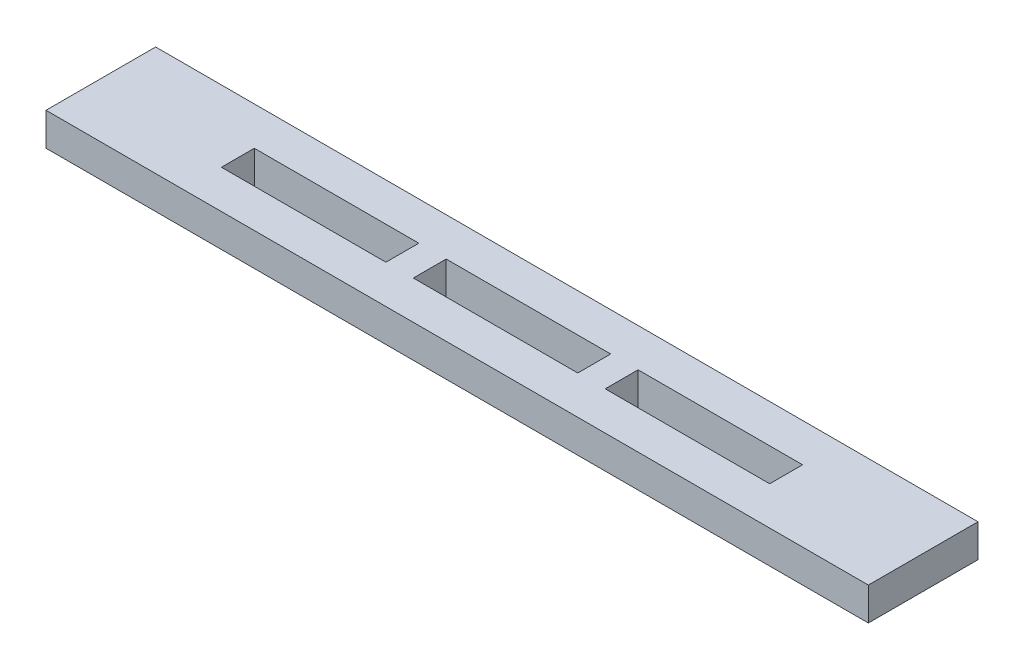
SolidWorks part; units mm, degrees
ref_plane "Front Plane" through (0, 0, 0) normal (0, 0, 1) x (1, 0, 0)
ref_plane "Top Plane" through (0, 0, 0) normal (0, 1, 0) x (1, 0, 0)
ref_plane "Right Plane" through (0, 0, 0) normal (1, 0, 0) x (0, 0, -1)
sketch "Sketch1" plane through (0, 0, 0) normal (0, 1, 0) x (1, 0, 0)
  line L1 (-75, 10) -> (75, 10)
  line L2 (-75, 10) -> (-75, -10)
  line L3 (-75, -10) -> (75, -10)
  line L4 (75, 10) -> (75, -10)
  line L5 (-75, 10) -> (75, -10) construction
  line L6 (-75, -10) -> (75, 10) construction
  point P0 (0, 0)
  dimension "D2" = 20
  dimension "D1" = 150
sketch "Sketch2" plane through (0, 0, 0) normal (0, 0, 1) x (1, 0, 0)
  line L0 (0, 0) -> (0, 6) construction
  line L1 (-75, 0) -> (75, 0) construction
extrude "Boss-Extrude1" add sketch "Sketch1" along normal up to vertex (6 mm away) contours L2 L3 L4 L1 up to point (0, 6, 0)
sketch "Sketch3" plane through (0, 6, 0) normal (0, 1, 0) x (1, 0, 0)
  line L0 (15, -3) -> (15, 3) construction
  line L1 (50, 3) -> (20, 3)
  line L2 (50, 3) -> (50, -3)
  line L3 (50, -3) -> (20, -3)
  line L4 (20, 3) -> (20, -3)
  line L5 (15, -3) -> (-15, -3)
  line L6 (15, -3) -> (15, 3)
  line L7 (15, 3) -> (-15, 3)
  line L8 (-15, -3) -> (-15, 3)
  line L10 (-50, 3) -> (-20, 3)
  line L11 (-50, 3) -> (-50, -3)
  line L12 (-50, -3) -> (-20, -3)
  line L13 (-20, 3) -> (-20, -3)
extrude "Cut-Extrude1" cut sketch "Sketch3" against normal through all
equation "\"glass_width\" = 150"
equation "\"glass_height\"= 100"
equation "\"glass_thickness\"= 4"
equation "\"brood_space\"= 42"
equation "\"t1\"= 6"
equation "\"t2\"= 3.2"
equation "\"box_depth\"= \"brood_space\" + \"glass_thickness\" + \"glass_thickness\" + \"t2\" + \"t2\""
equation "\"box_width\"= \"glass_width\" + \"t1\" + \"t1\""
equation "\"food_height\"= 70"
equation "\"box_height\" = \"glass_height\" + ( \"t1\" * 3 ) + \"food_height\""
equation "\"D1@Sketch2\"=\"t1\""
equation "\"D1@Sketch1\"=\"glass_width\""
